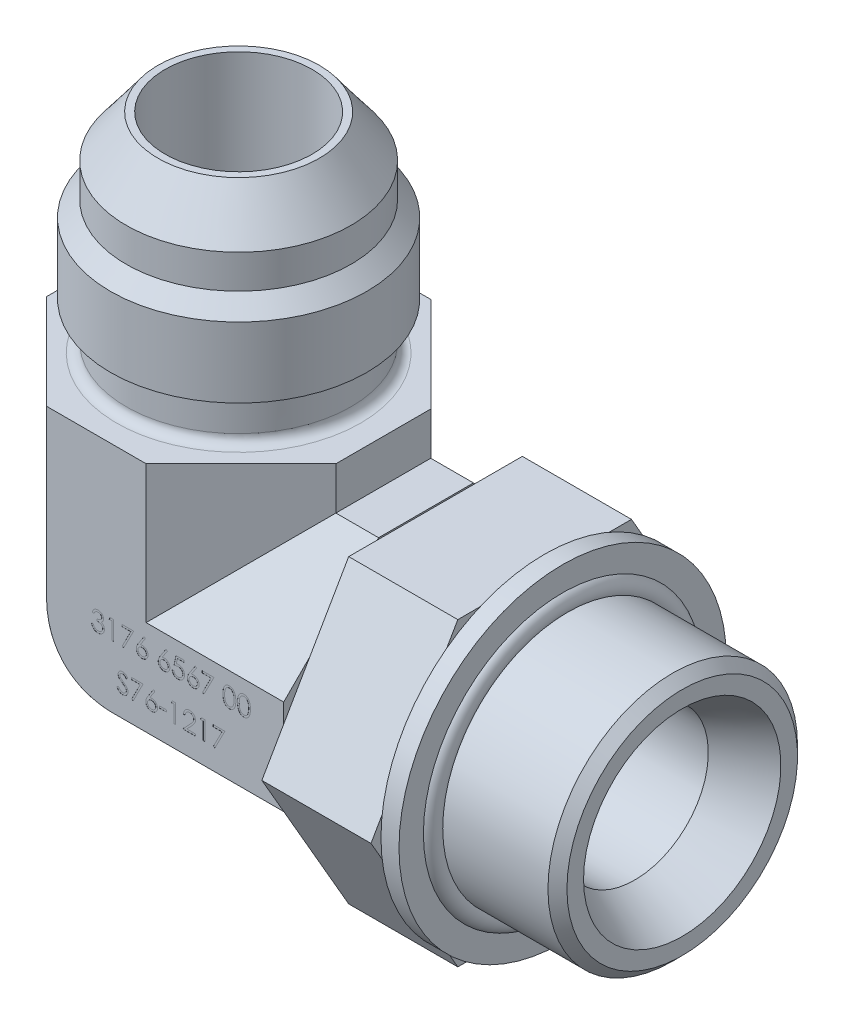
SolidWorks part; units mm, degrees
material "4140 H-T"
ref_plane "Front Plane" through (0, 0, 0) normal (0, 0, 1) x (1, 0, 0)
ref_plane "Top Plane" through (0, 0, 0) normal (0, 1, 0) x (1, 0, 0)
ref_plane "Right Plane" through (0, 0, 0) normal (1, 0, 0) x (0, 0, -1)
sketch "Sketch1" plane through (0, 0, 0) normal (0, 0, 1) x (1, 0, 0)
  line L1 (0, 0) -> (0, -30)
  line L2 (0, -30) -> (-35, -30)
  line L3 (-35, -30) -> (-35, 4.5)
  line L4 (-35, 4.5) -> (-4.5, 4.5)
  line L5 (-4.5, 4.5) -> (-4.5, 0)
  line L6 (-4.5, 0) -> (0, 0)
  dimension "D1" = 34.5
  dimension "D2" = 35
  dimension "D4" = 30
  dimension "D5" = 30.5
extrude "Extrude1" add sketch "Sketch1" along normal mid plane 30
sketch "Sketch3" plane through (0, 4.5, 0) normal (0, 1, 0) x (1, 0, 0)
  line L0 (-4.5, 0) -> (-35, 0) construction
  line L1 (-35, -15) -> (-35, 15) construction
  point P0 (-19.75, 0)
sketch "Sketch4" plane through (0, 0, 0) normal (0, 0, 1) x (1, 0, 0)
  line L0 (-19.75, 4.5) -> (-19.75, 18.0535) construction
  line L1 (-4.5, 4.5) -> (-35, 4.5) construction
  line L2 (-33.25, 9.4526) -> (-33.25, 16.85)
  line L3 (-33.25, 16.85) -> (-31.6, 18.5)
  line L4 (-31.6, 18.5) -> (-31.6, 22.0544)
  line L5 (-31.6, 22.0544) -> (-28.25, 26.5)
  line L6 (-28.25, 26.5) -> (-27.5, 26.5)
  line L7 (-27.5, 26.5) -> (-27.5, 4.5)
  line L8 (-31.6, 4.5) -> (-27.5, 4.5)
  line L9 (-33.25, 9.4526) -> (-31.6, 8.5)
  line L10 (-31.6, 8.5) -> (-31.6, 4.5)
  line L11 (-4.5, 4.5) -> (-35, 4.5) construction
  dimension "D1" = 27
  dimension "D2" = 23.7
  dimension "D3" = 15.5
  dimension "D4" = 37
  dimension "D5" = 4
  dimension "D6" = 22
  dimension "D7" = 17
  dimension "D8" = 45
  dimension "D9" = 8
  dimension "D10" = 60
revolve "Revolve1" add sketch "Sketch4" angle 360 about L0
cosmetic thread "Cosmetic Thread2" parameters "D2"=24.89
sketch "Sketch5" plane through (0, 0, 0) normal (0, 0, 1) x (1, 0, 0)
  line L0 (0, -15) -> (26.07, -15) construction
  line L2 (0, 0) -> (0, -30) construction
  line L3 (0, -1.85) -> (26, -1.85)
  line L4 (27, -2.85) -> (27, -4.6)
  line L5 (27, -4.6) -> (22, -7.25)
  line L6 (22, -7.25) -> (0, -7.25)
  line L7 (0, -1.85) -> (0, -7.25)
  line L8 (26, -1.85) -> (27, -2.85)
  dimension "D1" = 1
  dimension "D2" = 45
  dimension "D3" = 26.3
  dimension "D4" = 15.5
  dimension "D5" = 5
  dimension "D6" = 20.8
  dimension "D7" = 27
  dimension "D8" = 15
revolve "Revolve2" add sketch "Sketch5" angle 360 about L0
cosmetic thread "Cosmetic Thread1" parameters "D1"=28, "D2"=24
fillet "Fillet3" radius 1 2 edges at (0, -28.15, 0) (-7.9, 4.5, 0)
sketch "Sketch6" plane through (0, 0, 0) normal (0, 0, 1) x (1, 0, 0)
  line L0 (27, -15) -> (-31.1059, -15) construction
  line L1 (27, -27.15) -> (27, -2.85) construction
  line L2 (27, -7.25) -> (-18.3433, -7.25)
  line L3 (-18.3433, -7.25) -> (-23, -15)
  line L4 (27, -7.25) -> (27, -15)
  line L5 (22, -7.25) -> (0, -7.25) construction
  line L6 (27, -15) -> (-23, -15)
  dimension "D1" = 59
  dimension "D2" = 50
revolve "Cut-Revolve1" cut sketch "Sketch6" angle 360 about L0
sketch "Sketch7" plane through (0, 0, 0) normal (0, 0, 1) x (1, 0, 0)
  line L0 (-19.75, 18.0535) -> (-19.75, -19.5) construction
  line L1 (-19.75, 4.5) -> (-19.75, 18.0535) construction
  line L2 (-27.5, 26.5) -> (-27.5, -18.8433)
  line L3 (-27.5, 26.5) -> (-27.5, 4.5) construction
  line L4 (-27.5, -18.8433) -> (-19.75, -23.5)
  line L6 (-27.5, 26.5) -> (-19.75, 26.5)
  line L7 (-11.25, 26.5) -> (-28.25, 26.5) construction
  line L8 (-19.75, -23.5) -> (-19.75, 26.5)
  dimension "D1" = 59
  dimension "D2" = 50
revolve "Cut-Revolve2" cut sketch "Sketch7" angle 360 about L0
fillet "Fillet4" radius 10 1 edges at (-35, -30, 0)
chamfer "Chamfer1" distance 10 angle 45 2 edges at (-35, -7.75, 15) (-35, -7.75, -15)
sketch "Sketch8" plane through (0, 0, 0) normal (1, 0, 0) x (0, 0, -1)
  line L0 (-5, -30) -> (-15, -30)
  line L1 (-15, -30) -> (15, -30) construction
  line L2 (-15, -30) -> (-15, -20)
  line L3 (-15, -30) -> (-15, 0) construction
  line L4 (-15, -20) -> (-5, -30)
  line L5 (0, 0) -> (0, -33.4093) construction
  line L6 (15, -20) -> (5, -30)
  line L7 (15, -30) -> (15, -20)
  line L8 (5, -30) -> (15, -30)
  dimension "D1" = 10
  dimension "D2" = 10
extrude "Cut-Extrude1" cut sketch "Sketch8" against normal through all
fillet "Fillet5" radius 10 2 edges at (-28.5355, -23.5355, 11.4645) (-28.5355, -23.5355, -11.4645)
sketch "Sketch9" plane through (0, 0, 0) normal (1, 0, 0) x (0, 0, -1)
  line L1 (18.302, -15) -> (9.151, 0.85)
  line L2 (9.151, 0.85) -> (-9.151, 0.85)
  line L3 (-9.151, 0.85) -> (-18.302, -15)
  line L4 (-18.302, -15) -> (-9.151, -30.85)
  line L5 (-9.151, -30.85) -> (9.151, -30.85)
  line L6 (9.151, -30.85) -> (18.302, -15)
  circle A0 centre (0, -15) radius 15.85 construction
  dimension "D1" = 31.7
extrude "Boss-Extrude1" add sketch "Sketch9" along normal blind 12.5
sketch "Sketch10" plane through (0, 0, 0) normal (0, 0, 1) x (1, 0, 0)
  line L0 (12.5, -15) -> (33.3971, -15) construction
  line L1 (12.5, 0.85) -> (12.5, -15) construction
  circle A0 centre (13.75, -1.3873) radius 1.25
  dimension "D1" = 27.2254
  dimension "D2" = 2.5
revolve "Revolve3" add sketch "Sketch10" angle 360 about L0
sketch "Sketch13" plane through (0, 0, 0) normal (0, 0, 1) x (1, 0, 0)
  line L0 (12.5, -15) -> (33.7147, -15) construction
  line L1 (12.5, 0.85) -> (12.5, -15) construction
  line L2 (12.5, 2.25) -> (14.4, 2.25)
  line L3 (12.5, 2.25) -> (12.5, -0.5)
  line L4 (12.5, -0.5) -> (14.4, -0.5)
  line L5 (14.4, 2.25) -> (14.4, -0.5)
  dimension "D1" = 34.5
  dimension "D2" = 1.9
  dimension "D3" = 29
revolve "Revolve5" add sketch "Sketch13" angle 360 about L0
chamfer "Chamfer2" distance 10 angle 45 2 edges at (-4.5, 2.25, 15) (-4.5, 2.25, -15)
chamfer "Chamfer3" distance 10 angle 45 2 edges at (-7.25, 0, 15) (-7.25, 0, -15)
sketch "Sketch14" plane through (0, 0, 15) normal (0, 0, 1) x (1, 0, 0)
  line L0 (-20.8958, -13.4349) -> (-2.8405, -13.4349) construction
  text T0 "3176 6567 00\r\nS76-1217"
  dimension "D1" = 13.4349
extrude "Cut-Extrude2" cut sketch "Sketch14" against normal blind 0.01
sketch "Sketch15" plane through (0, 0, 0) normal (-1, 0, 0) x (0, 0, 1)
  line L6 (9.151, -30.85) -> (18.302, -15)
  line L7 (18.302, -15) -> (9.151, 0.85)
  line L8 (9.151, 0.85) -> (-9.151, 0.85)
  line L9 (-9.151, 0.85) -> (-18.302, -15)
  line L10 (-18.302, -15) -> (-9.151, -30.85)
  line L11 (-9.151, -30.85) -> (9.151, -30.85)
  line L12 (9.151, -30.85) -> (18.302, -15)
  line L13 (18.302, -15) -> (9.151, 0.85)
  line L14 (9.151, 0.85) -> (-9.151, 0.85)
  line L15 (-9.151, 0.85) -> (-18.302, -15)
  line L16 (-18.302, -15) -> (-9.151, -30.85)
  line L17 (-9.151, -30.85) -> (9.151, -30.85)
  circle A0 centre (0, -15) radius 13.15
  dimension "D2" = 26.3
  dimension "D1" = 0
extrude "Cut-Extrude3" cut sketch "Sketch15" against normal blind 1
sketch "Sketch16" plane through (12.5, 0, 0) normal (1, 0, 0) x (0, 0, -1)
  circle A0 centre (0, -15) radius 7.75
  circle A1 centre (0, -15) radius 7.75 construction
extrude "Cut-Extrude4" cut sketch "Sketch16" against normal blind 20
